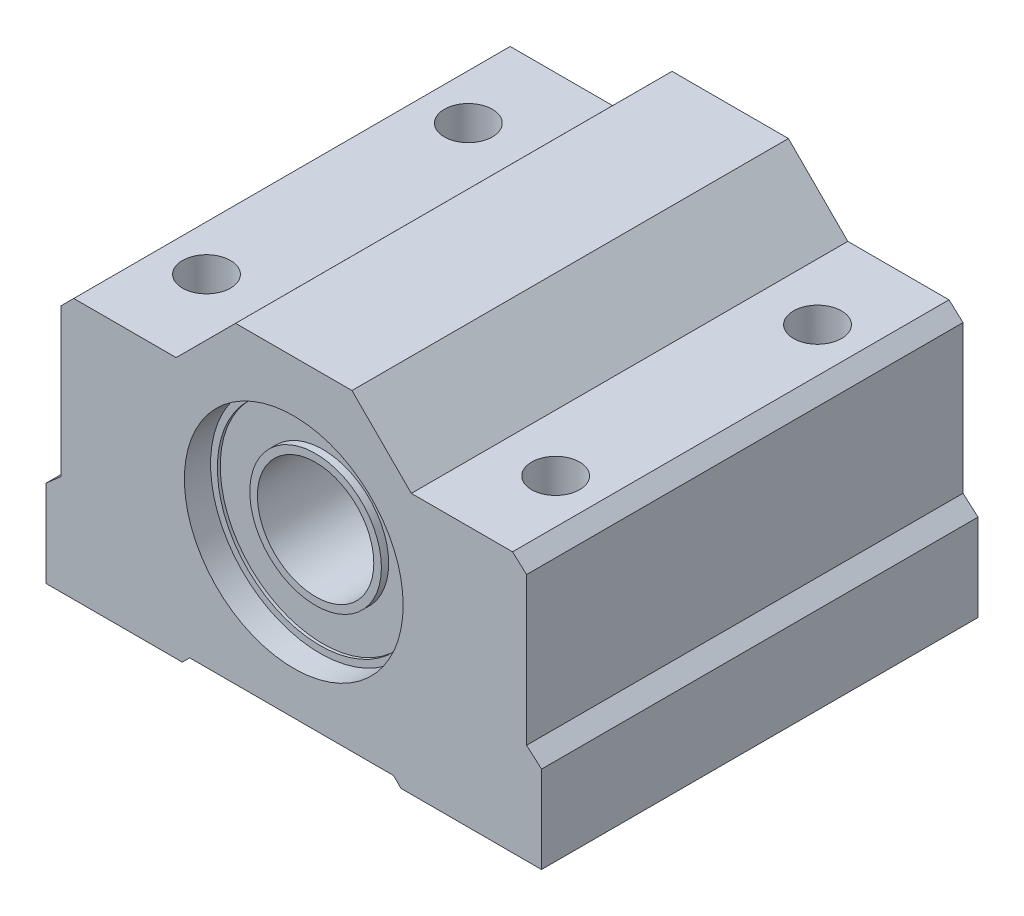
SolidWorks part; units mm, degrees
ref_plane "Plan de face" through (0, 0, 0) normal (0, 0, 1) x (1, 0, 0)
ref_plane "Plan de dessus" through (0, 0, 0) normal (0, 1, 0) x (1, 0, 0)
ref_plane "Plan de droite" through (0, 0, 0) normal (1, 0, 0) x (0, 0, -1)
sketch "Esquisse1" plane through (0, 0, 0) normal (0, 0, 1) x (1, 0, 0)
  line L0 (37.9997, 220.8672) -> (334.6664, 220.8672) construction
  line L1 (-17.03, -10.9738) -> (-7.6627, -10.9738)
  line L2 (-7.6627, -10.9738) -> (-7.1532, -10.4644)
  line L3 (-7.1532, -10.4644) -> (6.8576, -10.4644)
  line L4 (6.8576, -10.4644) -> (7.3671, -10.9738)
  line L5 (7.3671, -10.9738) -> (17.03, -10.9738)
  line L6 (17.03, -10.9738) -> (17.03, -4.9953)
  line L7 (17.03, -4.9953) -> (16.0028, -4.0892)
  line L8 (16.0028, -4.0892) -> (16.0028, 6.0714)
  line L9 (16.0028, 6.0714) -> (15.0375, 6.9443)
  line L10 (15.0375, 6.9443) -> (8.0819, 6.9443)
  line L11 (8.0819, 6.9443) -> (4, 11.0262)
  line L12 (4, 11.0262) -> (-4, 11.0262)
  line L13 (-4, 11.0262) -> (-8.0839, 6.9443)
  line L14 (-8.0839, 6.9443) -> (-15.1244, 6.9443)
  line L15 (-15.1244, 6.9443) -> (-15.9972, 6.0714)
  line L16 (-15.9972, 6.0714) -> (-15.9972, -4.0892)
  line L17 (-15.9972, -4.0892) -> (-17.03, -5.0045)
  line L18 (-17.03, -5.0045) -> (-17.03, -10.9738)
  circle A0 centre (0, 0) radius 4
  circle A1 centre (0, 0) radius 4.5234
  circle A2 centre (0, 0) radius 7.0518
  circle A3 centre (0, 0) radius 7.519
  dimension "D1" = 8
  dimension "D2" = 22
  dimension "D3" = 34.06
  dimension "D4" = 17.03
  dimension "D5" = 32
  dimension "D6" = 8
  dimension "D7" = 4
extrude "Boss.-Extru.1" add sketch "Esquisse1" against normal blind 30 contours L17 L18 L1 L2 L3 L4 L5 L6 L7 L8 L9 L10 L11 L12 L13 L14 L15 L16 A3 region at (-16.6245, -7.9891, 0)
extrude "Boss.-Extru.2" add sketch "Esquisse1<3>" against normal blind 28 separate body contours A2 A1 region at (-6.8523, 0, 0)
sketch "Esquisse1<3>" plane through (0, 0, 0) normal (0, 0, 1) x (1, 0, 0) same geometry as "Esquisse1"
extrude "Boss.-Extru.3" add sketch "Esquisse1<4>" against normal blind 30 contours A3 A2 region at (-7.3063, 0, 0)
sketch "Esquisse1<4>" plane through (0, 0, 0) normal (0, 0, 1) x (1, 0, 0) same geometry as "Esquisse1"
extrude "Boss.-Extru.4" add sketch "Esquisse1<5>" against normal blind 28.5 contours A1 A0 region at (-4.3955, 0, 0)
sketch "Esquisse1<5>" plane through (0, 0, 0) normal (0, 0, 1) x (1, 0, 0) same geometry as "Esquisse1"
extrude "Enlèv. mat.-Extru.1" cut sketch "Esquisse1<6>" against normal blind 1.5 contours A1 A0 region at (-4.3955, 0, 0)
sketch "Esquisse1<6>" plane through (0, 0, 0) normal (0, 0, 1) x (1, 0, 0) same geometry as "Esquisse1"
extrude "Enlèv. mat.-Extru.2" cut sketch "Esquisse1<7>" against normal blind 2 contours A2 A1 region at (-6.8523, 0, 0)
sketch "Esquisse1<7>" plane through (0, 0, 0) normal (0, 0, 1) x (1, 0, 0) same geometry as "Esquisse1"
extrude "Enlèv. mat.-Extru.3" cut sketch "Esquisse1<8>" against normal blind 1.8 contours A3 A2 region at (-7.3063, 0, 0)
sketch "Esquisse1<8>" plane through (0, 0, 0) normal (0, 0, 1) x (1, 0, 0) same geometry as "Esquisse1"
extrude "Enlèv. mat.-Extru.4" cut sketch "Esquisse1<9>" along normal blind 1.8 from surface contours A3 A2 region at (-7.3063, 0, 0) starting at face at (-0.0372, -1.1683, -30)
sketch "Esquisse1<9>" plane through (0, 0, 0) normal (0, 0, 1) x (1, 0, 0) same geometry as "Esquisse1"
sketch "Esquisse2" plane through (0, -10.9738, 0) normal (0, -1, 0) x (1, 0, 0)
  line L0 (74.1667, 293.5) -> (370.8333, 293.5) construction
  line L2 (-17.03, -30) -> (-17.03, 0) construction
  line L3 (12, -6) -> (12, 0) construction
  line L4 (7.3671, 0) -> (17.03, 0) construction
  line L5 (12, -24) -> (12, -30) construction
  line L6 (7.3671, -30) -> (17.03, -30) construction
  circle A0 centre (-12, -6) radius 1.65
  circle A1 centre (12, -6) radius 1.65
  circle A2 centre (12, -24) radius 1.65
  circle A3 centre (-12, -24) radius 1.65
  dimension "D1" = 3.3
  dimension "D2" = 3.3
  dimension "D3" = 3.3
  dimension "D4" = 3.3
  dimension "D10" = 18
  dimension "D5" = 0
  dimension "D6" = 0
  dimension "D7" = 0
  dimension "D8" = 0
  dimension "D9" = 24
  dimension "D11" = 6
  dimension "D12" = 5.03
  dimension "D13" = 6
extrude "Enlèv. mat.-Extru.5" cut sketch "Esquisse2" against normal blind 21.8
